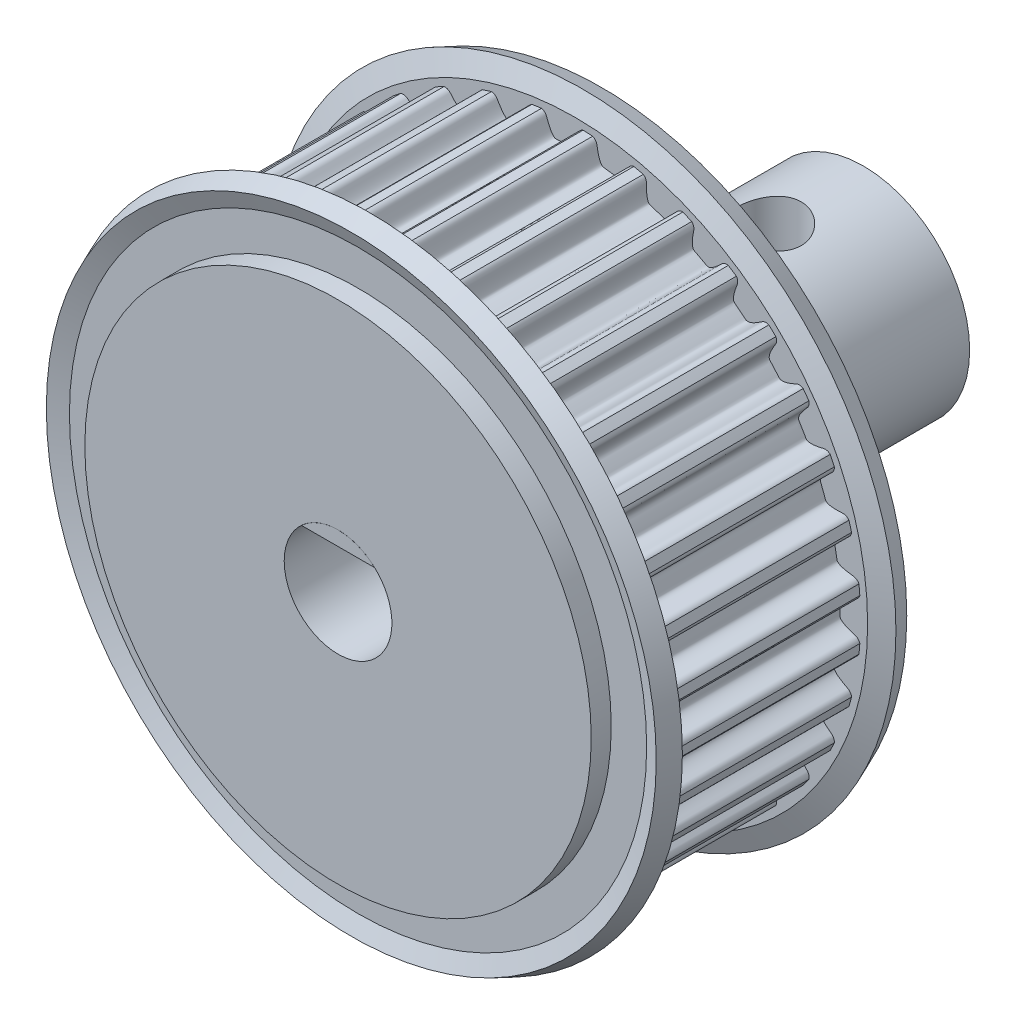
SolidWorks part; units mm, degrees
ref_plane "前视基准面" through (0, 0, 0) normal (0, 0, 1) x (1, 0, 0)
ref_plane "上视基准面" through (0, 0, 0) normal (0, 1, 0) x (1, 0, 0)
ref_plane "右视基准面" through (0, 0, 0) normal (1, 0, 0) x (0, 0, -1)
other "Configuration Table"
ref_axis "基准轴1" through (0, 0, 55) along (0, 0, -1)
sketch "SketchRevolveGearBelt01" plane through (0, 0, 0) normal (1, 0, 0) x (0, 0, -1)
  line L0 (0, 0) -> (1, 0) construction
  line L1 (5.274, 0) -> (5.274, 9.6408)
  line L2 (5.274, 9.6408) -> (4.512, 9.6408)
  line L3 (4.512, 9.6408) -> (4.512, 10.9893)
  line L4 (4.512, 10.9893) -> (4.7696, 11.6112)
  line L5 (4.7696, 11.6112) -> (4.0656, 11.9028)
  line L6 (4.0656, 11.9028) -> (3.75, 11.1408)
  line L7 (3.75, 11.1408) -> (3.75, 10.872)
  line L8 (3.75, 10.872) -> (-3.75, 10.872)
  line L9 (-3.75, 10.872) -> (-3.75, 11.1408)
  line L10 (-3.75, 11.1408) -> (-4.0656, 11.9028)
  line L11 (-4.0656, 11.9028) -> (-4.7696, 11.6112)
  line L12 (-4.7696, 11.6112) -> (-4.512, 10.9893)
  line L13 (-4.512, 10.9893) -> (-4.512, 9.6408)
  line L14 (-4.512, 9.6408) -> (-5.274, 9.6408)
  line L15 (-5.274, 9.6408) -> (-5.274, 0)
  line L16 (-5.274, 0) -> (5.274, 0)
  dimension "GearBeltFlange1OutsideLength" = 1.3484
  dimension "GearBeltFlange1X" = 0.2576
  dimension "GearBeltFlange1Y" = 0.622
  dimension "GearBeltFlangeThickness" = 0.762
  dimension "GearBeltFlangeInside" = 0.2688
  dimension "GearBeltOutsideDiameter" = 10.872
  dimension "GearBeltFlange2X" = 0.2576
revolve "Gates_PowerGrip_GT_2mm, 6mm Belt Width" add sketch "SketchRevolveGearBelt01" angle 360 about L0
sketch "SketchToothGearBelt01" plane through (0, 0, 0) normal (0, 0, 1) x (1, 0, 0)
  arc A0 (10.8521, 0.8621) -> (10.8521, -0.8621) centre (0, 0) cw
  spline S0 degree 3 poles (10.8521, -0.8621) (10.8522, -0.8446) (10.8499, -0.8185) (10.8418, -0.7846) (10.8333, -0.7598) (10.8224, -0.7361) (10.8092, -0.7135) (10.7939, -0.6923) (10.7765, -0.6727) (10.7574, -0.6549) (10.7366, -0.6391) (10.7143, -0.6254) (10.6908, -0.6138) (10.6531, -0.6004) (10.6046, -0.5857) (10.547, -0.5675) (10.4946, -0.5498) (10.4453, -0.5322) (10.3992, -0.5145) (10.3562, -0.4969) (10.3165, -0.4793) (10.2799, -0.4616) (10.2465, -0.444) (10.2162, -0.4264) (10.1891, -0.4087) (10.1652, -0.3911) (10.1444, -0.3735) (10.1268, -0.3558) (10.1123, -0.3381) (10.101, -0.3203) (10.0929, -0.3025) (10.0879, -0.2846) (10.0857, -0.2503) (10.0889, -0.2) (10.089, -0.1333) (10.0898, -0.0667) (10.0899, 0) (10.0898, 0.0667) (10.089, 0.1333) (10.0889, 0.2) (10.0857, 0.2503) (10.0879, 0.2846) (10.0929, 0.3025) (10.101, 0.3203) (10.1123, 0.3381) (10.1268, 0.3558) (10.1444, 0.3735) (10.1652, 0.3911) (10.1891, 0.4087) (10.2162, 0.4264) (10.2465, 0.444) (10.2799, 0.4616) (10.3165, 0.4793) (10.3562, 0.4969) (10.3992, 0.5145) (10.4453, 0.5322) (10.4946, 0.5498) (10.547, 0.5675) (10.6046, 0.5857) (10.6531, 0.6004) (10.6908, 0.6138) (10.7143, 0.6254) (10.7366, 0.6391) (10.7574, 0.6549) (10.7765, 0.6727) (10.7939, 0.6923) (10.8092, 0.7135) (10.8224, 0.7361) (10.8333, 0.7598) (10.8418, 0.7846) (10.8499, 0.8185) (10.8522, 0.8446) (10.8521, 0.8621) knots 0 0 0 0 0.020006 0.030009 0.040012 0.050015 0.060018 0.070022 0.080025 0.090028 0.100031 0.110034 0.120037 0.13004 0.155933 0.178284 0.199479 0.219524 0.238427 0.256199 0.272852 0.288401 0.302863 0.316262 0.328625 0.339989 0.350401 0.35992 0.368626 0.376623 0.384043 0.391052 0.397847 0.423404 0.448936 0.474468 0.5 0.525532 0.551064 0.576596 0.602153 0.608948 0.615957 0.623377 0.631374 0.64008 0.649599 0.660011 0.671375 0.683738 0.697137 0.711599 0.727148 0.743801 0.761573 0.780476 0.800521 0.821716 0.844067 0.86996 0.879963 0.889966 0.899969 0.909972 0.919975 0.929978 0.939982 0.949985 0.959988 0.969991 0.979994 1 1 1 1
extrude "ToothExtrudeCutGearBelt01" cut sketch "SketchToothGearBelt01" against normal blind 3.75 and the other way blind 3.75
pattern_circular "Tooth Pattern, 35" count 35 every 10.286 about axis through (0, 0, 55) along (0, 0, -1) of "ToothExtrudeCutGearBelt01"
sketch "BoreRevolveSketch" plane through (0, 0, 0) normal (1, 0, 0) x (0, 0, -1)
  line L0 (0, 0) -> (1, 0) construction
  line L1 (-5.274, 0) -> (5.274, 0)
  line L2 (5.274, 0) -> (5.274, 5)
  line L3 (5.274, 5) -> (-5.274, 5)
  line L4 (-5.274, 5) -> (-5.274, 0)
  dimension "TaperSide1" = 5
  dimension "TaperSide2" = 5
revolve "BoreRevolveCut" cut sketch "BoreRevolveSketch" angle 360 about L0
sketch "AuxiliarySketchGearBelt01" plane through (0, 0, 0) normal (0, 0, 1) x (1, 0, 0)
  circle A0 centre (0, 0) radius 11.1408 construction
  dimension "PitchDiameter" = 22.2817
sketch "草图5" plane through (0, 0, 5.274) normal (0, 0, 1) x (1, 0, 0)
  circle A0 centre (0, 0) radius 5
extrude "凸台-拉伸1" add sketch "草图5" against normal blind 10
sketch "草图6" plane through (0, 0, -4.726) normal (0, 0, -1) x (-1, 0, 0)
  circle A0 centre (0, 0) radius 2.05
  circle A1 centre (0, 0) radius 4.05
  dimension "D1" = 4.1
  dimension "D2" = 2
extrude "凸台-拉伸2" add sketch "草图6" along normal blind 10
sketch "草图7" plane through (0, 0, -4.726) normal (0, 0, -1) x (-1, 0, 0)
  circle A0 centre (0, 0) radius 2.05
extrude "切除-拉伸2" cut sketch "草图7" against normal blind 10
sketch "草图8" plane through (0, 0, -14.726) normal (0, 0, -1) x (-1, 0, 0)
  line L0 (0, 0) -> (0, 1.5)
  line L1 (-1000, 1.5) -> (49000, 1.5)
  circle A0 centre (0, 0) radius 2.0472
  dimension "D1" = 1.5
extrude "凸台-拉伸3" add sketch "草图8" against normal blind 20 separate body contours L1 A0 region at (0, 1.7216, -14.726)
sketch "草图9" plane through (0, 1.5, 0) normal (0, -1, 0) x (1, 0, 0)
  line L0 (0, 55) -> (0, -55) construction
  circle A0 centre (0, -11.1094) radius 1.25
  dimension "D1" = 2.5
extrude "切除-拉伸6" cut sketch "草图9" against normal through all
